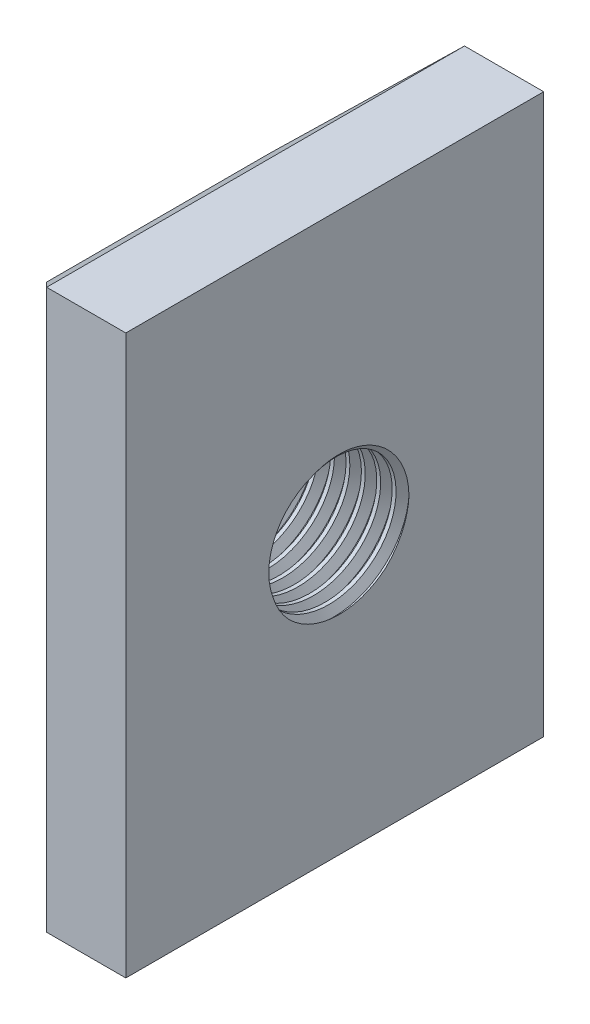
SolidWorks part; units mm, degrees
material "ABS"
ref_plane "Front Plane" through (0, 0, 0) normal (0, 0, 1) x (1, 0, 0)
ref_plane "Top Plane" through (0, 0, 0) normal (0, 1, 0) x (1, 0, 0)
ref_plane "Right Plane" through (0, 0, 0) normal (1, 0, 0) x (0, 0, -1)
sketch "Sketch1" plane through (0, 0, 0) normal (0, 0, 1) x (1, 0, 0)
  line L0 (0, -6.35) -> (0, 6.35)
  line L1 (0, 6.35) -> (-1.8, 6.35)
  line L2 (-1.8, 6.35) -> (-4.0071, 4.245)
  line L3 (-4.0071, 4.245) -> (-4.0071, -4.245)
  line L4 (-4.0071, -4.245) -> (-1.8, -6.35)
  line L5 (-1.8, -6.35) -> (0, -6.35)
  point P4 (0, 0)
  dimension "D1" = 12.7
  dimension "D2" = 8.49
  dimension "D3" = 3.05
  dimension "D4" = 1.8
extrude "Boss-Extrude1" add sketch "Sketch1" along normal mid plane 9.5
chamfer "Chamfer1" distance 2.2 angle 45 1 edges at (-4.0071, 0, 4.75)
chamfer "Chamfer2" distance 2.2 angle 45 1 edges at (-4.0071, 0, -4.75)
sketch "Sketch2" plane through (0, 0, 0) normal (1, 0, 0) x (0, 0, -1)
  circle A0 centre (0, 0) radius 1.5
  dimension "D1" = 3
extrude "Cut-Extrude1" cut sketch "Sketch2" against normal through all
thread "Thread1" pitch 0.35 method cut profile "Thread Profile1" start angle 0, offset 1, length 10, pitch 0.35, diameter 3
ref_plane "Plane1" through (-5.0071, 0, -1.5) normal (0, -1, 0) x (0, 0, -1)
sketch "Thread Profile1" plane through (-5.0071, 0, -1.5) normal (0, -1, 0) x (0, 0, -1)
  line L0 (0, 0) -> (0, 0.35) construction
  line L1 (0, 0) -> (0.1894, 0.1094)
  line L2 (0.1894, 0.1094) -> (0.1894, 0.1531)
  line L3 (0.1894, 0.1531) -> (0, 0.2625)
  line L4 (0.1894, 0.1312) -> (0, 0.1312) construction
  line L11 (0, 0) -> (0, 0.2625)
  point P2 (0, 0)
  dimension "Pitch" = 0.35
  dimension "Profile_Angle" = 60
  dimension "Profile_Land" = 0.0437
  dimension "Profile_Height" = 0.1894
